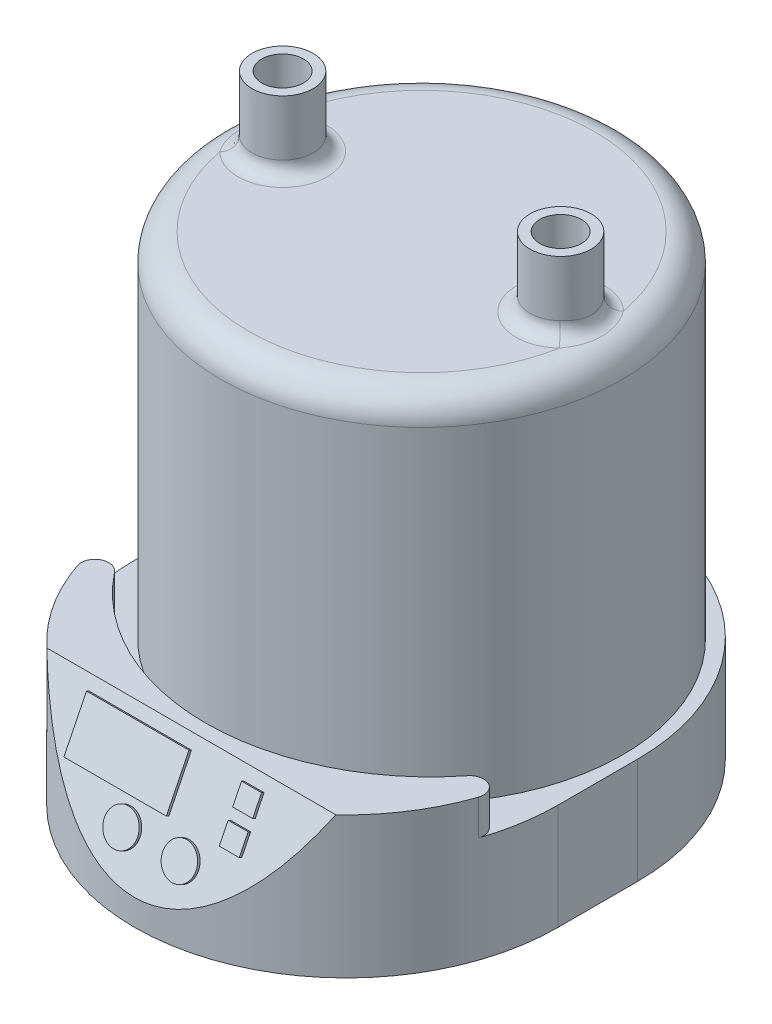
SolidWorks part; units mm, degrees
material "PET"
ref_plane "Front" through (0, 0, 0) normal (0, 0, 1) x (1, 0, 0)
ref_plane "Top" through (0, 0, 0) normal (0, 1, 0) x (1, 0, 0)
ref_plane "Right" through (0, 0, 0) normal (1, 0, 0) x (0, 0, -1)
ref_axis "Axis1" through (0, 0, 55) along (0, 0, -1)
sketch "Sketch1" plane through (0, 0, 0) normal (0, 1, 0) x (1, 0, 0)
  line L0 (0, 14.2875) -> (0, -14.2875) construction
  line L1 (76.2, 14.2875) -> (76.2, -14.2875)
  line L2 (-76.2, 14.2875) -> (-76.2, -14.2875)
  arc A0 (76.2, 14.2875) -> (-76.2, 14.2875) centre (0, 14.2875) ccw
  arc A1 (-76.2, -14.2875) -> (76.2, -14.2875) centre (0, -14.2875) ccw
  point P2 (0, 0)
  dimension "D1" = 76.2
  dimension "D2" = 28.575
extrude "Boss-Extrude1" add sketch "Sketch1" along normal blind 50.8
sketch "Sketch2" plane through (0, 50.8, 0) normal (0, 1, 0) x (1, 0, 0)
  line L0 (0, -90.4875) -> (0, 90.4875) construction
  arc A0 (-76.2, -14.2875) -> (76.2, -14.2875) centre (0, -14.2875) ccw construction
  arc A1 (76.2, 14.2875) -> (-76.2, 14.2875) centre (0, 14.2875) ccw construction
  circle A2 centre (0, 16.0971) radius 80.9625
  dimension "D1" = 161.925
  dimension "D2" = 106.5846
extrude "Cut-Extrude1" cut sketch "Sketch2" against normal blind 12.7
sketch "Sketch3" plane through (0, 0, 0) normal (1, 0, 0) x (0, 0, -1)
  line L0 (0, 0) -> (0, 38.1) construction
  line L1 (-14.2875, 0) -> (14.2875, 0) construction
  line L2 (-11.2614, 38.1) -> (14.2875, 38.1) construction
  line L3 (0, 38.1) -> (-90.4875, 38.1) construction
  line L4 (-90.4875, 50.8) -> (-90.4875, 0) construction
  line L5 (-76.2778, 38.1) -> (-68.0758, 54.7145)
  line L6 (-68.0758, 54.7145) -> (-114.1723, 54.7145)
  line L7 (-114.1723, 54.7145) -> (-99.1883, -8.3084)
  line L8 (-76.2778, 38.1) -> (-99.1883, -8.3084)
  dimension "D1" = 68.0758
  dimension "D2" = 76.2778
  dimension "D3" = 99.1883
  dimension "D4" = 114.1723
  dimension "D5" = 54.7145
extrude "Cut-Extrude2" cut sketch "Sketch3" against normal mid plane 254
sketch "Sketch4" plane through (0, 38.1, 0) normal (0, 1, 0) x (1, 0, 0)
  line L0 (0, -64.8654) -> (0, 90.4875) construction
  arc A0 (-76.2, -11.2614) -> (76.2, -11.2614) centre (0, 16.0971) ccw construction
  arc A1 (76.2, 14.2875) -> (-76.2, 14.2875) centre (0, 14.2875) ccw construction
  circle A2 centre (0, 12.811) radius 72.1989
  point P10 (0, 12.811)
  dimension "D1" = 144.3979
extrude "Boss-Extrude2" add sketch "Sketch4" along normal blind 127
sketch "Sketch5" plane through (0, 165.1, 0) normal (0, 1, 0) x (1, 0, 0)
  line L0 (-72.1989, 12.811) -> (72.1989, 12.811) construction
  line L1 (0, 12.811) -> (0, 85.01) construction
  circle A0 centre (0, 12.811) radius 72.1989 construction
  circle A1 centre (0, 12.811) radius 72.1989 construction
  circle A2 centre (-50, 12.811) radius 11
  circle A3 centre (50, 12.811) radius 11
  circle A4 centre (-50, 12.811) radius 7.5
  circle A5 centre (50, 12.811) radius 7.5
  dimension "D1" = 22
  dimension "D2" = 15
  dimension "D3" = 50
extrude "Boss-Extrude3" add sketch "Sketch5" along normal blind 25
sketch "Sketch6" plane through (0, 37.7431, 76.454) normal (0, 0.4427, 0.8967) x (1, 0, 0)
  line L0 (-10.5, -16.8766) -> (10.5, -16.8766) construction
  line L1 (-34.8863, 10.1975) -> (1.959, 10.1975)
  line L2 (-34.8863, 10.1975) -> (-34.8863, -8.1724)
  line L3 (-34.8863, -8.1724) -> (1.959, -8.1724)
  line L4 (1.959, 10.1975) -> (1.959, -8.1724)
  line L5 (-34.8863, 10.1975) -> (1.959, -8.1724) construction
  line L6 (-34.8863, -8.1724) -> (1.959, 10.1975) construction
  line L7 (0, -16.8766) -> (0, 14.5613) construction
  line L8 (51.9773, 14.5613) -> (-51.9773, 14.5613) construction
  line L9 (24.5307, -4.438) -> (24.5307, 6.4631) construction
  line L10 (20.9333, 10.0605) -> (28.1282, 10.0605)
  line L11 (20.9333, 10.0605) -> (20.9333, 2.8657)
  line L12 (20.9333, 2.8657) -> (28.1282, 2.8657)
  line L13 (28.1282, 10.0605) -> (28.1282, 2.8657)
  line L14 (20.9333, 10.0605) -> (28.1282, 2.8657) construction
  line L15 (20.9333, 2.8657) -> (28.1282, 10.0605) construction
  line L16 (20.9333, -0.8406) -> (28.1282, -0.8406)
  line L17 (20.9333, -0.8406) -> (20.9333, -8.0354)
  line L18 (20.9333, -8.0354) -> (28.1282, -8.0354)
  line L19 (28.1282, -0.8406) -> (28.1282, -8.0354)
  line L20 (20.9333, -0.8406) -> (28.1282, -8.0354) construction
  line L21 (20.9333, -8.0354) -> (28.1282, -0.8406) construction
  line L22 (1.959, 1.0126) -> (24.5307, 1.0126) construction
  circle A0 centre (-10.5, -16.8766) radius 6
  circle A1 centre (10.5, -16.8766) radius 6
  point P0 (-16.4636, 1.0126)
  point P13 (0, 14.5613)
  point P14 (24.5307, -4.438)
  point P15 (24.5307, 6.4631)
  dimension "D1" = 12
  dimension "D2" = 21
  dimension "D3" = 23.8491
  dimension "D4" = 27.4466
  dimension "D5" = 50.0183
  dimension "D6" = 68.4409
  dimension "D7" = 4.3637
  dimension "D8" = 4.5007
  dimension "D9" = 13.5487
  dimension "D16" = 31.4379
extrude "Boss-Extrude4" add sketch "Sketch6" along normal blind 1
fillet "Fillet1" radius 10 1 edges at (0, 165.1, 59.3879)
fillet "Fillet2" radius 5 2 edges at (-50, 165.1, -1.811) (50, 165.1, -1.811)
fillet "Fillet3" radius 5 2 edges at (-76.2, 44.45, 11.2614) (76.2, 44.45, 11.2614)
